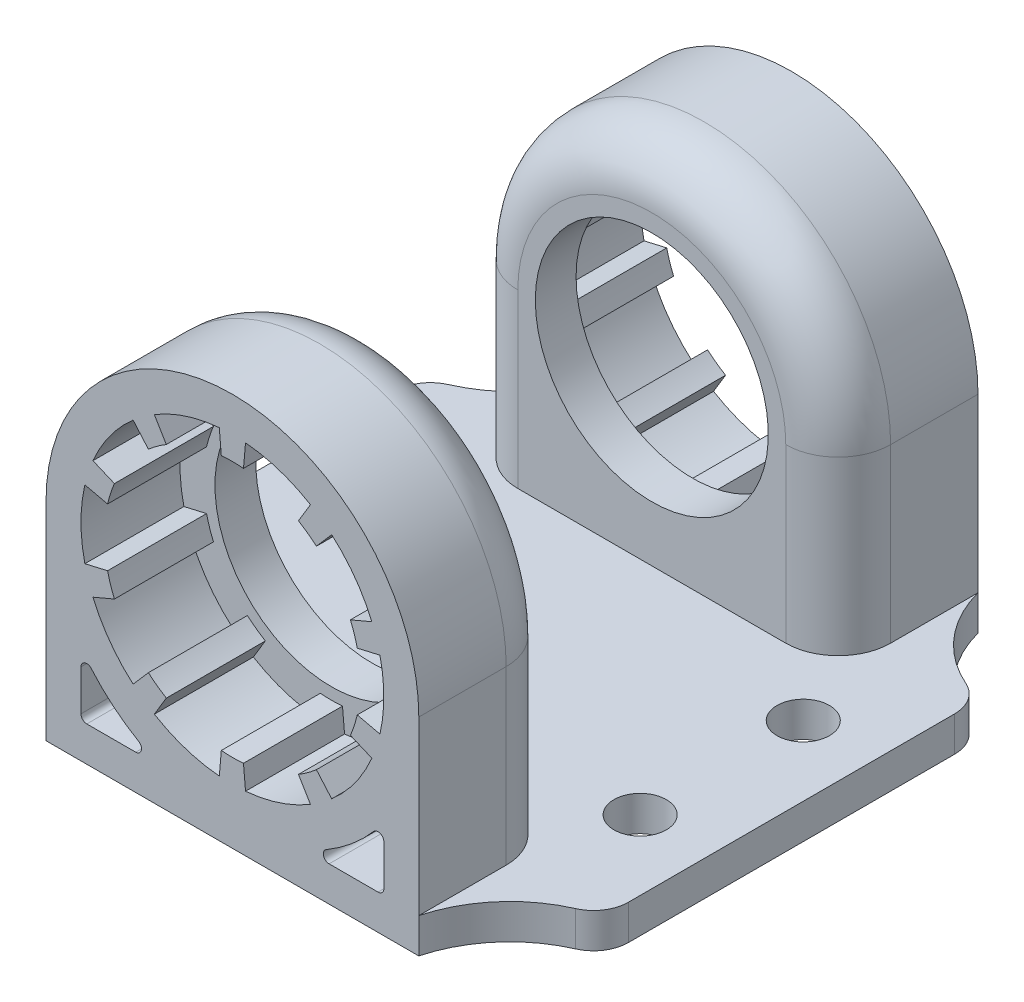
SolidWorks part; units mm, degrees
ref_plane "Alzado" through (0, 0, 0) normal (0, 0, 1) x (1, 0, 0)
ref_plane "Planta" through (0, 0, 0) normal (0, 1, 0) x (1, 0, 0)
ref_plane "Vista lateral" through (0, 0, 0) normal (1, 0, 0) x (0, 0, -1)
sketch "Croquis2" plane through (0, 0, 0) normal (0, 0, 1) x (1, 0, 0)
  line L1 (0, 0) -> (-32, 0)
  line L2 (0, 0) -> (0, 17.76)
  line L4 (-32, 0) -> (-32, 17.76)
  arc A0 (0, 17.76) -> (-32, 17.76) centre (-16, 17.76) ccw
  dimension "D1" = 32
  dimension "D2" = 17.76
extrude "Saliente-Extruir1" add sketch "Croquis2" along normal mid plane 12
sketch "Croquis3" plane through (0, 0, 6) normal (0, 0, 1) x (1, 0, 0)
  circle A0 centre (-16, 17.76) radius 4
  dimension "D1" = 8
extrude "Cortar-Extruir1" cut sketch "Croquis3" against normal through all
ref_plane "Plano1" through (-16, 0, 0) normal (-1, 0, 0) x (0, 0, 1)
sketch "Croquis4" plane through (0, 0, 6) normal (0, 0, 1) x (1, 0, 0)
  circle A0 centre (-16, 17.76) radius 13
  dimension "D1" = 26
extrude "Cortar-Extruir2" cut sketch "Croquis4" against normal blind 8.5
sketch "Croquis5" plane through (0, 0, -2.5) normal (0, 0, 1) x (1, 0, 0)
  circle A0 centre (-16, 17.76) radius 10
  dimension "D1" = 20
extrude "Cortar-Extruir3" cut sketch "Croquis5" against normal blind 8.5
sketch "Croquis6" plane through (0, 0, -6) normal (0, 0, -1) x (-1, 0, 0)
  line L0 (32, 17.76) -> (32, 0) construction
  line L1 (0, 0) -> (32, 0)
  line L2 (0, 0) -> (0, 3)
  line L3 (0, 3) -> (32, 3)
  line L4 (32, 0) -> (32, 3)
  dimension "D1" = 3
extrude "Saliente-Extruir2" add sketch "Croquis6" along normal blind 24
ref_plane "Plano2" through (0, 0, -18) normal (0, 0, -1) x (-1, 0, 0)
mirror "Simetría1" about plane through (0, 0, -18) normal (0, 0, -1) of "Cortar-Extruir3", "Cortar-Extruir2", "Saliente-Extruir1"
sketch "Croquis7" plane through (0, 0, 0) normal (0, 1, 0) x (1, 0, 0)
  line L0 (0, 42) -> (0, 30) construction
  line L1 (0, 35) -> (5, 35)
  line L2 (0, 35) -> (0, 1)
  line L3 (0, 1) -> (5, 1)
  line L4 (8, 32) -> (8, 4)
  line L5 (0, 42) -> (-32, 42) construction
  line L6 (-32, -6) -> (0, -6) construction
  line L7 (-16, 42) -> (-16, 38.616) construction
  line L8 (-32, 1) -> (-37, 1)
  line L9 (-40, 32) -> (-40, 4)
  line L10 (-32, 35) -> (-37, 35)
  line L11 (-32, 35) -> (-32, 1)
  arc A0 (5, 1) -> (8, 4) centre (5, 4) ccw
  arc A1 (5, 35) -> (8, 32) centre (5, 32) cw
  arc A2 (-37, 1) -> (-40, 4) centre (-37, 4) cw
  arc A3 (-37, 35) -> (-40, 32) centre (-37, 32) ccw
  dimension "D4" = 3
  dimension "D1" = 7
  dimension "D2" = 7
  dimension "D3" = 8
extrude "Saliente-Extruir3" add sketch "Croquis7" along normal blind 3
fillet "Redondeo1" radius 11 4 edges at (0, 1.5, -35) (0, 1.5, -1) (-32, 1.5, -1) (-32, 1.5, -35)
sketch "Croquis8" plane through (0, 3, 0) normal (0, 1, 0) x (1, 0, 0)
  line L0 (8, 4) -> (8, 32) construction
  line L2 (17.6, 18) -> (-17.6, 18) construction
  circle A0 centre (2, 25) radius 2.25
  circle A1 centre (2, 11) radius 2.25
  dimension "D1" = 4.5
  dimension "D2" = 6
  dimension "D3" = 7
extrude "Cortar-Extruir4" cut sketch "Croquis8" against normal through all
mirror "Simetría2" about plane through (-16, 0, 0) normal (-1, 0, 0) of "Cortar-Extruir4"
sketch "Croquis11" plane through (0, 0, 6) normal (0, 0, 1) x (1, 0, 0)
  line L0 (-17.125, 30.7112) -> (-16.9519, 28.7187)
  line L1 (-14.875, 30.7112) -> (-15.0481, 28.7187)
  line L2 (-16, 30.76) -> (-16, 28.76) construction
  circle A0 centre (-16, 17.76) radius 16 construction
  arc A2 (-15.0481, 28.7187) -> (-16.9519, 28.7187) centre (-16, 17.76) ccw
  circle A3 centre (-16, 17.76) radius 13 construction
  arc A4 (-14.875, 30.7112) -> (-17.125, 30.7112) centre (-16, 17.76) ccw
  dimension "D1" = 32
  dimension "D2" = 2.25
  dimension "D3" = 22
extrude "Saliente-Extruir4" add sketch "Croquis11" against normal up to surface (8.5 mm away) up to face at (-6, 17.76, -2.5)
pattern_circular "MatrizC1" count 10 every 36 about axis through (-16, 17.76, 6) along (0, 0, 1) of "Saliente-Extruir4"
mirror "Simetría3" about plane through (0, 0, -18) normal (0, 0, -1) of "MatrizC1", "Saliente-Extruir4"
fillet "Redondeo2" radius 4.5 6 edges at (0, 10.38, -6) (-32, 10.38, -6) (-16, 33.76, -6) (0, 10.38, -30) (-32, 10.38, -30) (-16, 33.76, -30)
sketch "Croquis12" plane through (0, 0, 6) normal (0, 0, 1) x (1, 0, 0)
  line L0 (-3, 3.5) -> (-3, 6.9897)
  line L1 (0, 3) -> (0, 17.76) construction
  line L2 (-3.5, 3) -> (-7.6993, 3)
  line L3 (-32, 0) -> (0, 0) construction
  arc A0 (-7.9508, 3.9321) -> (-3.8788, 7.316) centre (-16, 17.76) ccw
  arc A1 (-3, 3.5) -> (-3.5, 3) centre (-3.5, 3.5) cw
  arc A2 (-3, 6.9897) -> (-3.8788, 7.316) centre (-3.5, 6.9897) ccw
  arc A3 (-7.6993, 3) -> (-7.9508, 3.9321) centre (-7.6993, 3.5) cw
  dimension "D3" = 32
  dimension "D4" = 0.5
  dimension "D1" = 3
  dimension "D2" = 3
extrude "Cortar-Extruir5" cut sketch "Croquis12" against normal blind 9
mirror "Simetría4" about plane through (-16, 0, 0) normal (-1, 0, 0) of "Cortar-Extruir5"
mirror "Simetría5" about plane through (0, 0, -18) normal (0, 0, -1) of "Simetría4", "Cortar-Extruir5"
